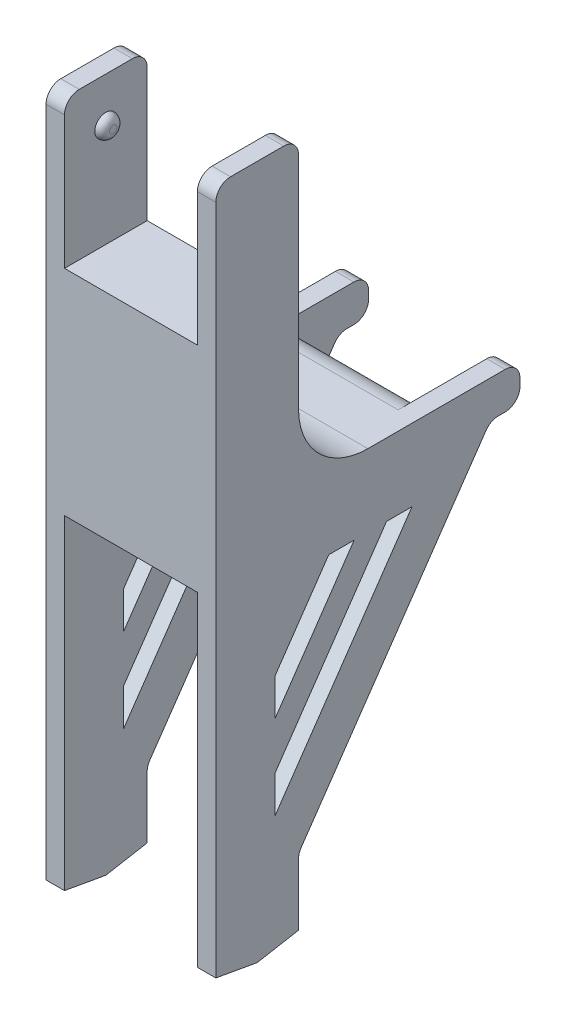
SolidWorks part; units mm, degrees
ref_plane "Front Plane" through (0, 0, 0) normal (0, 0, 1) x (1, 0, 0)
ref_plane "Top Plane" through (0, 0, 0) normal (0, 1, 0) x (1, 0, 0)
ref_plane "Right Plane" through (0, 0, 0) normal (1, 0, 0) x (0, 0, -1)
sketch "Szkic1" plane through (0, 0, 0) normal (1, 0, 0) x (0, 0, -1)
  line L2 (0, 0) -> (-10.3, 0)
  line L5 (-15, 4.7) -> (-15, 20.6)
  line L6 (-15, 20.6) -> (-20.6, 20.6)
  line L7 (-20.6, 20.6) -> (-20.6, -21.4)
  line L8 (0, 0) -> (0, -2.5)
  line L9 (0, -2.5) -> (-2, -2.5)
  line L10 (-2, -2.5) -> (-15, -21.4)
  line L11 (-15, -21.4) -> (-15, -25.9)
  line L13 (-20.6, -25.9) -> (-20.6, -21.4)
  line L20 (-20.6, -25.9) -> (-17.8, -26.4)
  line L21 (-17.8, -26.4) -> (-15, -25.9)
  arc A0 (-15, 4.7) -> (-10.3, 0) centre (-10.3, 4.7) ccw
  point P15 (-10.3, 4.7)
  dimension "D5" = 2.5
  dimension "D7" = 4.7
  dimension "D1" = 42
  dimension "D2" = 20.6
  dimension "D3" = 15.9
  dimension "D4" = 5.6
  dimension "D6" = 2
  dimension "D8" = 18.9
  dimension "D9" = 4.5
  dimension "D10" = 0.5
  dimension "D11" = 4.5
extrude "Dodanie-wyciągnięcie1" add sketch "Szkic1" along normal blind 11.5
ref_plane "Płaszczyzna dolna" through (0, 0, 20.6) normal (0, 0, 1) x (1, 0, 0)
sketch "Szkic2" plane through (0, 0, 20.6) normal (0, 0, 1) x (1, 0, 0)
  line L0 (5.75, 20.6) -> (5.75, -25.9) construction
  line L1 (11.5, 20.6) -> (0, 20.6) construction
  line L4 (10.25, 10.6) -> (1.25, 10.6)
  line L5 (10.25, 10.6) -> (10.25, 20.6)
  line L6 (10.25, 20.6) -> (1.25, 20.6)
  line L7 (1.25, 10.6) -> (1.25, 20.6)
  line L8 (10.25, 10.6) -> (1.25, 20.6) construction
  line L9 (10.25, 20.6) -> (1.25, 10.6) construction
  line L10 (10.25, -3.9) -> (1.25, -3.9)
  line L11 (10.25, -3.9) -> (10.25, -28.2703)
  line L12 (10.25, -28.2703) -> (1.25, -28.2703)
  line L13 (1.25, -3.9) -> (1.25, -28.2703)
  line L14 (10.25, -3.9) -> (1.25, -28.2703) construction
  line L15 (10.25, -28.2703) -> (1.25, -3.9) construction
  point P6 (5.75, 15.6)
  point P11 (5.75, -14.9)
  dimension "D1" = 9
  dimension "D2" = 10
  dimension "D3" = 9
  dimension "D4" = 11
extrude "Wytnij-wyciągnięcie1" cut sketch "Szkic2" against normal through all
ref_plane "Płaszczyzna boczna" through (11.5, 0, 0) normal (1, 0, 0) x (0, 0, -1)
sketch "Szkic3" plane through (11.5, 0, 0) normal (1, 0, 0) x (0, 0, -1)
  line L0 (-16.6, -12.7056) -> (-16.6, -10.1985)
  line L1 (-16.6, -10.1985) -> (-12.9555, -4.9)
  line L2 (-12.9555, -4.9) -> (-11.2311, -4.9)
  line L3 (-11.2311, -4.9) -> (-16.6, -12.7056)
  line L4 (-16.6, -15.8972) -> (-16.6, -18.4043)
  line L5 (-16.6, -18.4043) -> (-7.3113, -4.9)
  line L6 (-7.3113, -4.9) -> (-9.0358, -4.9)
  line L7 (-9.0358, -4.9) -> (-16.6, -15.8972)
  line L8 (-15, -21.4) -> (-2, -2.5) construction
  line L10 (-20.6, 6.325) -> (-20.6, -6.325) construction
  dimension "D1" = 4
  dimension "D2" = 21
extrude "Wytnij-wyciągnięcie2" cut sketch "Szkic3" against normal through all both and the other way through all
ref_plane "Płaszczyzna3" through (0, 0, 0) normal (0, 1, 0) x (1, 0, 0)
sketch "Szkic4" plane through (0, 0, 0) normal (0, 1, 0) x (1, 0, 0)
  line L0 (5.75, -5) -> (5.75, 0) construction
  line L2 (11.5, 0) -> (0, 0) construction
  line L4 (1.25, -5) -> (10.25, -5)
  line L5 (1.25, -5) -> (1.25, 0)
  line L6 (1.25, 0) -> (10.25, 0)
  line L7 (10.25, -5) -> (10.25, 0)
  line L8 (1.25, -5) -> (10.25, 0) construction
  line L9 (1.25, 0) -> (10.25, -5) construction
  point P6 (5.75, -2.5)
  dimension "D1" = 9
  dimension "D2" = 5
extrude "Wytnij-wyciągnięcie3" cut sketch "Szkic4" against normal blind 10
fillet "Zaokrąglenie1" radius 2 2 edges at (5.75, -3.9, 5) (5.75, 0, 5)
fillet "Zaokrąglenie2" radius 1 12 edges at (0.625, 0, 0) (0.625, -2.5, 0) (10.875, -2.5, 0) (10.875, 0, 0) (10.875, 20.6, 20.6) (10.875, 20.6, 15) (0.625, 20.6, 20.6) (0.625, 20.6, 15) (0.625, -2.5, 2) (10.875, -2.5, 2) (0.625, -21.4, 15) (10.875, -21.4, 15)
ref_plane "Płaszczyzna4" through (10.25, 0, 0) normal (-1, 0, 0) x (0, 0, 1)
sketch "Szkic5" plane through (10.25, 0, 0) normal (-1, 0, 0) x (0, 0, 1)
  line L3 (17.8, 20.6) -> (17.8, 10.6) construction
  line L4 (16, 20.6) -> (19.6, 20.6) construction
  line L5 (15, 10.6) -> (20.6, 10.6) construction
  circle A0 centre (17.8, 17.6) radius 0.75
  dimension "D1" = 1.5
  dimension "D2" = 3
extrude "Dodanie-wyciągnięcie2" add sketch "Szkic5" along normal blind 0.5
fillet "Zaokrąglenie3" radius 0.5 1 edges at (9.75, 16.85, 17.8)
ref_plane "Płaszczyzna5" through (5.75, 0, 0) normal (1, 0, 0) x (0, 0, -1)
mirror "Lustro2" about plane through (5.75, 0, 0) normal (1, 0, 0) of bodies 113 115
